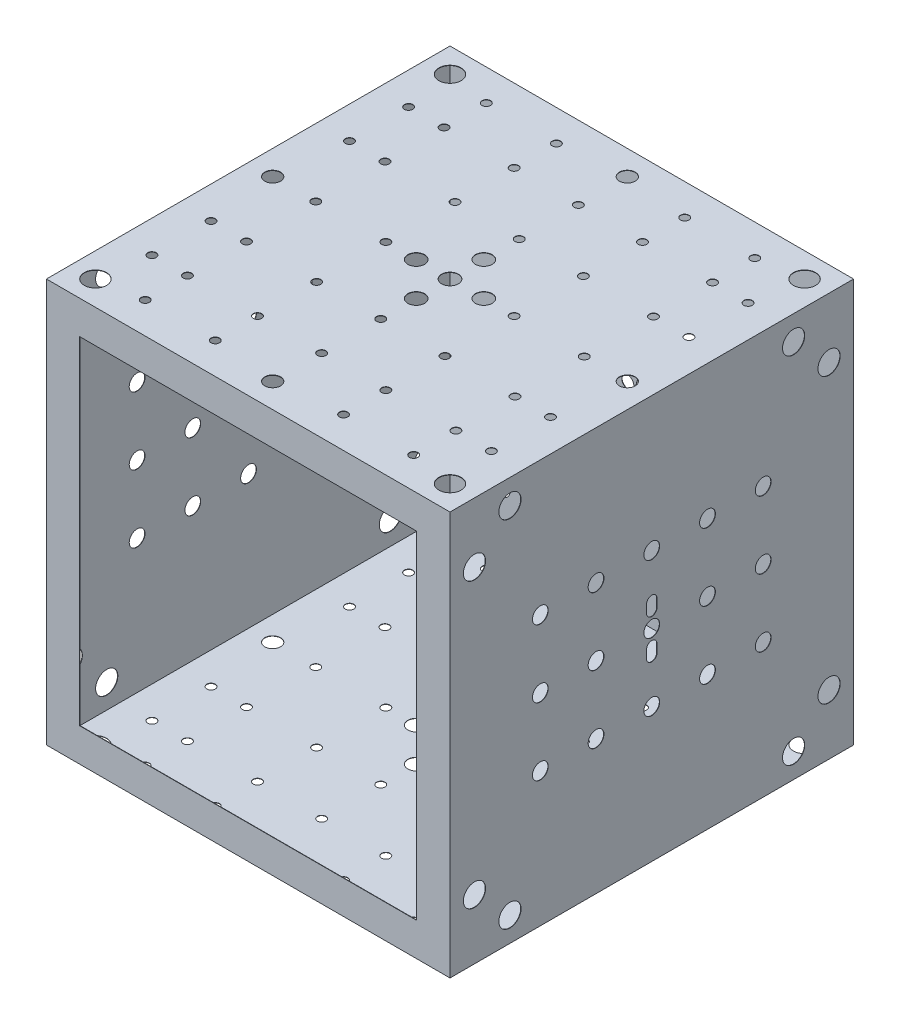
SolidWorks part; units mm, degrees
ref_plane "Front" through (0, 0, 0) normal (0, 0, 1) x (1, 0, 0)
ref_plane "Top" through (0, 0, 0) normal (0, 1, 0) x (1, 0, 0)
ref_plane "Right" through (0, 0, 0) normal (1, 0, 0) x (0, 0, -1)
sketch "Sketch1" plane through (0, 0, 0) normal (0, 1, 0) x (1, 0, 0)
  line L1 (-1195, 1195) -> (1195, 1195)
  line L2 (-1195, 1195) -> (-1195, -1195)
  line L3 (-1195, -1195) -> (1195, -1195)
  line L4 (1195, 1195) -> (1195, -1195)
  line L5 (-1195, 1195) -> (1195, -1195) construction
  line L6 (-1195, -1195) -> (1195, 1195) construction
  point P0 (0, 0)
  dimension "D1" = 2390
  dimension "D2" = 2390
extrude "Boss-Extrude1" add sketch "Sketch1" along normal blind 2390
sketch "Sketch7" plane through (0, 0, 1195) normal (0, 0, 1) x (1, 0, 0)
  line L0 (-1195, 1195) -> (1195, 1195) construction
  line L1 (-1195, 2390) -> (-1195, 0) construction
  line L2 (1195, 2390) -> (1195, 0) construction
  line L3 (0, 2390) -> (0, 0) construction
  line L4 (-1195, 2390) -> (1195, 2390) construction
  line L5 (-1195, 0) -> (1195, 0) construction
  line L7 (-1193, 2388) -> (1193, 2388)
  line L8 (-1193, 2388) -> (-1193, 2)
  line L9 (-1193, 2) -> (1193, 2)
  line L10 (1193, 2388) -> (1193, 2)
  line L11 (-1193, 2388) -> (1193, 2) construction
  line L12 (-1193, 2) -> (1193, 2388) construction
  point P12 (0, 1195)
  dimension "D1" = 2
  dimension "D2" = 2
extrude "Cut-Extrude2" cut sketch "Sketch7" against normal blind 2388
sketch "Sketch10" plane through (0, 0, 1195) normal (0, 0, 1) x (1, 0, 0)
  line L0 (0, 0) -> (0, 2388) construction
  line L1 (1193, 2388) -> (-1193, 2388) construction
  line L2 (1195, 1195) -> (-1195, 1195) construction
  line L3 (1195, 2390) -> (1195, 0) construction
  line L4 (-1195, 2390) -> (-1195, 0) construction
  line L6 (-1195, 2388) -> (1195, 2388)
  line L7 (-1195, 2388) -> (-1195, 0)
  line L8 (-1195, 0) -> (1195, 0)
  line L9 (1195, 2388) -> (1195, 0)
  line L10 (-1195, 2388) -> (1195, 0) construction
  line L11 (-1195, 0) -> (1195, 2388) construction
  line L12 (-997.835, 2193) -> (997.835, 2193)
  line L13 (-997.835, 2193) -> (-997.835, 197)
  line L14 (-997.835, 197) -> (997.835, 197)
  line L15 (997.835, 2193) -> (997.835, 197)
  line L16 (-997.835, 2193) -> (997.835, 197) construction
  line L17 (-997.835, 197) -> (997.835, 2193) construction
  point P11 (0, 1194)
  point P17 (0, 1195)
  dimension "D1" = 195
extrude "Boss-Extrude4" add sketch "Sketch10" against normal blind 2
sketch "Sketch11" plane through (0, 2390, 0) normal (0, 1, 0) x (1, 0, 0)
  line L0 (0, -1195) -> (0, 1195) construction
  line L1 (-1195, -1195) -> (1195, -1195) construction
  line L2 (1195, 1195) -> (-1195, 1195) construction
  line L3 (-1195, 0) -> (1195, 0) construction
  line L4 (-1195, 1195) -> (-1195, -1195) construction
  line L5 (1195, -1195) -> (1195, 1195) construction
  line L6 (0, 0) -> (-1195, 1195) construction
  line L7 (0, 0) -> (200, 0) construction
  line L8 (0, 0) -> (0, 200) construction
  line L9 (-380, 0) -> (-380, 410) construction
  line L10 (-795, 410) -> (-795, 760) construction
  line L11 (-795, 760) -> (-795, 1010) construction
  circle A0 centre (0, 0) radius 49.85
  circle A1 centre (200, 0) radius 49.85
  circle A2 centre (-200, 0) radius 49.85
  circle A4 centre (0, 200) radius 49.85
  circle A5 centre (0, -200) radius 49.85
  circle A6 centre (-380, 0) radius 25
  circle A7 centre (-795, 0) radius 25
  circle A8 centre (-1050, 0) radius 46.75
  circle A9 centre (-1050, 1050) radius 65.8
  circle A10 centre (380, 0) radius 25
  circle A11 centre (795, 0) radius 25
  circle A12 centre (1050, 0) radius 46.75
  circle A13 centre (1050, 1050) radius 65.8
  circle A14 centre (-380, 410) radius 25
  circle A15 centre (-795, 410) radius 25
  circle A16 centre (380, 410) radius 25
  circle A17 centre (795, 410) radius 25
  circle A18 centre (0, 410) radius 25
  circle A19 centre (-795, 760) radius 25
  circle A20 centre (-380, 760) radius 25
  circle A21 centre (0, 760) radius 25
  circle A22 centre (380, 760) radius 25
  circle A23 centre (795, 760) radius 25
  circle A24 centre (-795, 1010) radius 25
  circle A25 centre (-380, 1010) radius 25
  circle A26 centre (380, 1010) radius 25
  circle A27 centre (795, 1010) radius 25
  circle A28 centre (0, 1050) radius 46.75
  circle A29 centre (-1005, 760) radius 25
  circle A30 centre (-1005, 410) radius 25
  circle A31 centre (1005, 410) radius 25
  circle A32 centre (1005, 760) radius 25
  circle A33 centre (1005, -410) radius 25
  circle A34 centre (795, -410) radius 25
  circle A35 centre (380, -410) radius 25
  circle A36 centre (0, -410) radius 25
  circle A37 centre (-380, -410) radius 25
  circle A38 centre (-795, -410) radius 25
  circle A39 centre (-1005, -410) radius 25
  circle A40 centre (-1005, -760) radius 25
  circle A41 centre (-795, -760) radius 25
  circle A42 centre (-380, -760) radius 25
  circle A43 centre (0, -760) radius 25
  circle A44 centre (380, -760) radius 25
  circle A45 centre (795, -760) radius 25
  circle A46 centre (1005, -760) radius 25
  circle A47 centre (1050, -1050) radius 65.8
  circle A48 centre (795, -1010) radius 25
  circle A49 centre (380, -1010) radius 25
  circle A50 centre (0, -1050) radius 46.75
  circle A51 centre (-380, -1010) radius 25
  circle A52 centre (-795, -1010) radius 25
  circle A53 centre (-1050, -1050) radius 65.8
  dimension "D1" = 99.7
  dimension "D7" = 50
  dimension "D8" = 50
  dimension "D10" = 93.5
  dimension "D12" = 131.6
  dimension "D16" = 50
  dimension "D22" = 93.5
  dimension "D24" = 50
  dimension "D27" = 50
  dimension "D3" = 200
  dimension "D5" = 200
  dimension "D6" = 380
  dimension "D9" = 795
  dimension "D11" = 1050
  dimension "D13" = 1050
  dimension "D14" = 2
  dimension "D15" = 410
  dimension "D17" = 410
  dimension "D19" = 350
  dimension "D21" = 250
  dimension "D23" = 1050
  dimension "D25" = 1005
  dimension "D26" = 760
  dimension "D28" = 350
  dimension "D29" = 210
  dimension "D2" = 2
  dimension "D4" = 2
  dimension "D18" = 2
  dimension "D20" = 2
extrude "Cut-Extrude3" cut sketch "Sketch11" against normal through all
sketch "Sketch12" plane through (0, 0, -1195) normal (0, 0, -1) x (-1, 0, 0)
  line L0 (-1195, 1195) -> (1195, 1195) construction
  line L1 (-1195, 2390) -> (-1195, 0) construction
  line L2 (1195, 2390) -> (1195, 0) construction
  line L3 (0, 2390) -> (0, 26.3654) construction
  line L4 (-1195, 2390) -> (1195, 2390) construction
  line L5 (0, 1195) -> (-1195, 2390) construction
  line L6 (0, 1195) -> (1195, 2390) construction
  circle A0 centre (0, 1195) radius 91.2
  circle A1 centre (0, 1335) radius 35.635
  circle A2 centre (-900, 2095) radius 65.8
  circle A3 centre (-222, 1577) radius 91.2
  circle A4 centre (222, 813) radius 91.2
  circle A5 centre (900, 2095) radius 65.8
  circle A6 centre (900, 295) radius 65.8
  circle A7 centre (-900, 295) radius 65.8
  circle A8 centre (-140, 1195) radius 35.635
  circle A9 centre (0, 1055) radius 35.635
  circle A10 centre (140, 1195) radius 35.635
  dimension "D1" = 182.4
  dimension "D2" = 71.27
  dimension "D4" = 131.6
  dimension "D6" = 182.4
  dimension "D11" = 182.4
  dimension "D3" = 140
  dimension "D5" = 900
  dimension "D7" = 222
  dimension "D8" = 382
  dimension "D9" = 222
  dimension "D10" = 382
extrude "Cut-Extrude4" cut sketch "Sketch12" against normal through all
sketch "Sketch13" plane through (-1195, 0, 0) normal (-1, 0, 0) x (0, 0, 1)
  line L0 (-1195, 1195) -> (1195, 1195) construction
  line L1 (0, 1055) -> (0, 1102.5) construction
  line L2 (30.9375, 1055) -> (30.9375, 1102.5)
  line L3 (-30.9375, 1055) -> (-30.9375, 1102.5)
  line L5 (0, 1335) -> (0, 1287.5) construction
  line L6 (30.9375, 1335) -> (30.9375, 1287.5)
  line L7 (-30.9375, 1335) -> (-30.9375, 1287.5)
  line L8 (0, 1195) -> (0, 1595) construction
  line L9 (0, 1595) -> (-330, 1595) construction
  line L10 (-1195, 2390) -> (1195, 0) construction
  line L12 (-1195, 2390) -> (-1195, 0) construction
  line L13 (1195, 2390) -> (1195, 0) construction
  line L15 (0, 2390) -> (0, 0) construction
  line L16 (-1195, 2390) -> (1195, 2390) construction
  circle A0 centre (0, 1195) radius 46.75
  arc A1 (30.9375, 1335) -> (-30.9375, 1335) centre (0, 1335) ccw
  arc A2 (-30.9375, 1287.5) -> (30.9375, 1287.5) centre (0, 1287.5) ccw
  circle A3 centre (0, 1595) radius 46.75
  circle A4 centre (-330, 1595) radius 46.75
  circle A5 centre (-330, 1195) radius 46.75
  circle A6 centre (-660, 1595) radius 46.75
  circle A7 centre (-660, 1195) radius 46.75
  circle A8 centre (-840, 2245) radius 65.8
  circle A9 centre (-1050, 2035) radius 65.8
  circle A10 centre (330, 1595) radius 46.75
  circle A11 centre (330, 1195) radius 46.75
  circle A12 centre (660, 1195) radius 46.75
  circle A13 centre (660, 1595) radius 46.75
  circle A14 centre (840, 2245) radius 65.8
  circle A15 centre (1050, 2035) radius 65.8
  circle A16 centre (-660, 795) radius 46.75
  circle A17 centre (-330, 795) radius 46.75
  circle A18 centre (0, 795) radius 46.75
  circle A19 centre (330, 795) radius 46.75
  circle A20 centre (660, 795) radius 46.75
  circle A21 centre (1050, 355) radius 65.8
  circle A22 centre (840, 145) radius 65.8
  circle A23 centre (-840, 145) radius 65.8
  circle A24 centre (-1050, 355) radius 65.8
  arc A25 (30.9375, 1055) -> (-30.9375, 1055) centre (0, 1055) cw
  arc A26 (-30.9375, 1102.5) -> (30.9375, 1102.5) centre (0, 1102.5) cw
  point P15 (0, 1311.25)
  point P73 (0, 1078.75)
  dimension "D1" = 93.5
  dimension "D3" = 30.9375
  dimension "D9" = 131.6
  dimension "D13" = 1195
  dimension "D2" = 92.5
  dimension "D4" = 47.5
  dimension "D6" = 400
  dimension "D8" = 330
  dimension "D10" = 1050
  dimension "D11" = 840
  dimension "D12" = 0
  dimension "D14" = 1195
  dimension "D15" = 116.25
  dimension "D5" = 2
  dimension "D7" = 3
extrude "Cut-Extrude5" cut sketch "Sketch13" against normal through all
